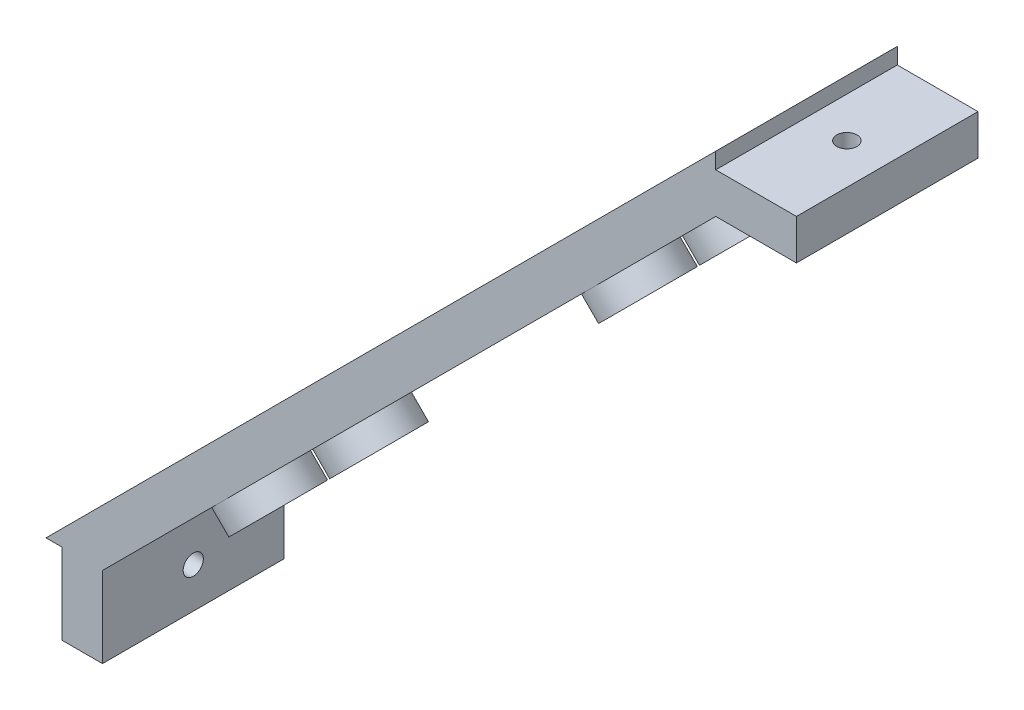
SolidWorks part; units mm, degrees
ref_plane "Front Plane" through (0, 0, 0) normal (0, 0, 1) x (1, 0, 0)
ref_plane "Top Plane" through (0, 0, 0) normal (0, 1, 0) x (1, 0, 0)
ref_plane "Right Plane" through (0, 0, 0) normal (1, 0, 0) x (0, 0, -1)
sketch "Sketch1" plane through (0, 0, 0) normal (0, 0, 1) x (1, 0, 0)
  line L0 (-41.5, -41.5) -> (41.5, 41.5)
  line L1 (41.5, 41.5) -> (41.5, 39.5)
  line L2 (-39.5, -41.5) -> (-39.5, -51.5)
  line L3 (-39.5, -51.5) -> (-34.5, -51.5)
  line L4 (41.5, 39.5) -> (51.5, 39.5)
  line L5 (-34.5, -51.5) -> (-34.5, -41.5)
  line L6 (-41.5, -41.5) -> (-39.5, -41.5)
  line L7 (-34.5, -41.5) -> (41.5, 34.5)
  line L8 (41.5, 34.5) -> (51.5, 34.5)
  line L9 (51.5, 39.5) -> (51.5, 34.5)
  point P13 (0, 0)
  dimension "D6" = 81
  dimension "D1" = 45
  dimension "D2" = 10
  dimension "D3" = 5
  dimension "D4" = 81
  dimension "D5" = 117.3797
  dimension "D7" = 2
extrude "Main" add sketch "Sketch1" along normal mid plane 22.5
sketch "Sketch2" plane through (41.5, 0, 0) normal (1, 0, 0) x (0, 0, -1)
  line L0 (11.25, -41.5) -> (-11.25, -51.5) construction
  line L1 (-11.25, -41.5) -> (11.25, -51.5) construction
  circle A0 centre (0, -46.5) radius 1.25
  dimension "D1" = 2.5
extrude "FixHole1" cut sketch "Sketch2" against normal through all
sketch "Sketch3" plane through (0, -41.5, 0) normal (0, -1, 0) x (-1, 0, 0)
  line L4 (-41.5, 11.25) -> (-51.5, -11.25) construction
  line L5 (-41.5, -11.25) -> (-51.5, 11.25) construction
  circle A1 centre (-46.5, 0) radius 1.25
  dimension "D1" = 2.5
extrude "FixHole2" cut sketch "Sketch3" against normal through all
sketch "Sketch6" plane through (3.5, -3.5, 0) normal (-0.7071, 0.7071, 0) x (0, 0, 1)
  line L0 (-11.25, 58.6899) -> (-11.25, -58.6899) construction
  circle A0 centre (-6.25, 40) radius 1.25
  point P4 (0, 0)
  dimension "D1" = 2.5
  dimension "D2" = 40
  dimension "D3" = 5
extrude "Cut-Extrude2" cut sketch "Sketch6" along normal through all
pattern_linear "LPattern1" count 5 spacing 20 along (-0.7071, -0.7071, 0) of "Cut-Extrude2"
sketch "Sketch7" plane through (3.5, -3.5, 0) normal (-0.7071, 0.7071, 0) x (0, 0, 1)
  line L0 (-11.25, 58.6899) -> (-11.25, -58.6899) construction
  circle A0 centre (-6.25, -33.0085) radius 5
  circle A1 centre (-6.25, 31.7915) radius 5
  dimension "D1" = 10
  dimension "D2" = 64.8
  dimension "D3" = 32.4
  dimension "D4" = 5
extrude "Boss-Extrude1" add sketch "Sketch7" against normal blind 3
sketch "Sketch8" plane through (5.6213, -5.6213, 0) normal (0.7071, -0.7071, 0) x (0, 0, -1)
  circle A0 centre (6.25, 31.7915) radius 1.25
  circle A1 centre (6.25, 31.7915) radius 5 construction
  circle A2 centre (6.25, -33.0085) radius 1.25
  circle A4 centre (6.25, -33.0085) radius 5 construction
  dimension "D1" = 2.5
extrude "Cut-Extrude3" cut sketch "Sketch8" against normal through all
pattern_linear "LPattern2" count 2 spacing 12.5 along (0, 0, 1) of "LPattern1", "Boss-Extrude1", "Cut-Extrude3"
